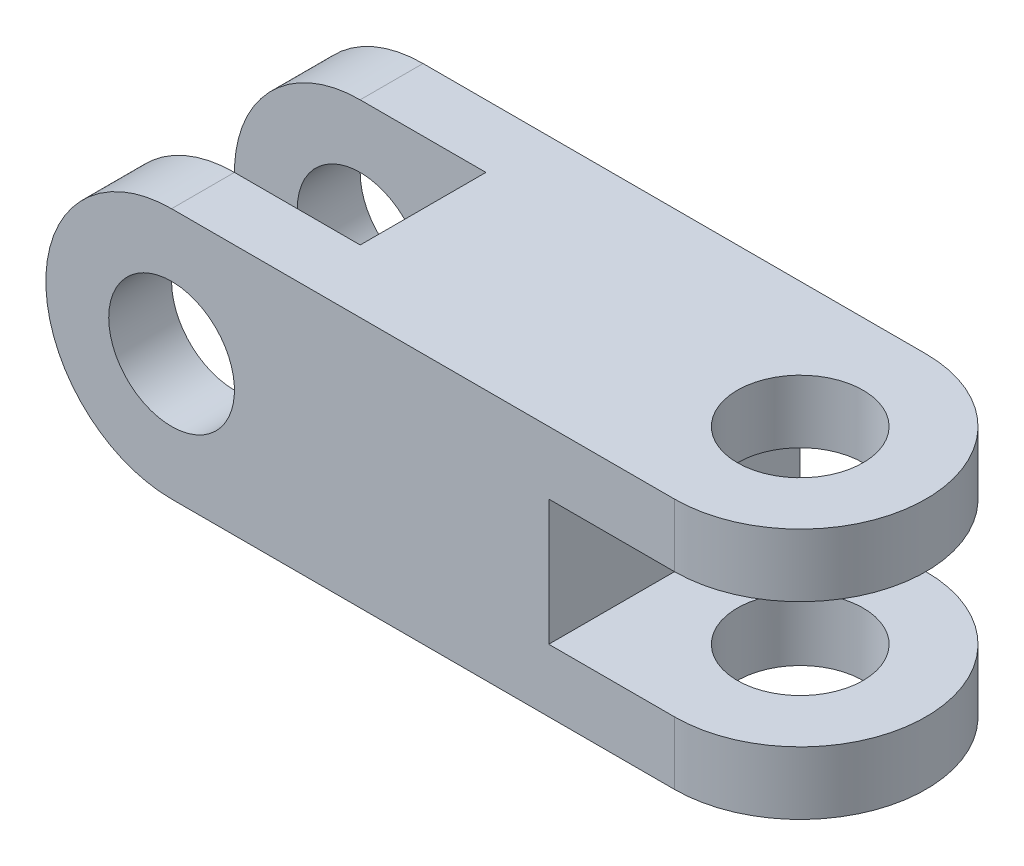
SolidWorks part; units mm, degrees
ref_plane "Plan de face" through (0, 0, 0) normal (0, 0, 1) x (1, 0, 0)
ref_plane "Plan de dessus" through (0, 0, 0) normal (0, 1, 0) x (1, 0, 0)
ref_plane "Plan de droite" through (0, 0, 0) normal (1, 0, 0) x (0, 0, -1)
sketch "Esquisse1" plane through (0, 0, 0) normal (0, 0, 1) x (1, 0, 0)
  line L0 (50, 5) -> (50, 15) construction
  line L1 (0, 0) -> (50, 0)
  line L2 (0, 0) -> (0, 20) construction
  line L3 (0, 20) -> (50, 20)
  line L4 (50, 0) -> (50, 5)
  line L5 (50, 15) -> (30, 15)
  line L6 (50, 15) -> (50, 5) construction
  line L7 (50, 5) -> (30, 5)
  line L8 (30, 15) -> (30, 5)
  line L9 (50, 15) -> (50, 20)
  arc A0 (0, 0) -> (0, 20) centre (0, 10) cw
  circle A1 centre (0, 10) radius 5
  point P11 (50, 10)
  point P12 (50, 10)
  dimension "D2" = 10
  dimension "D1" = 20
  dimension "D3" = 50
  dimension "D4" = 10
  dimension "D5" = 20
extrude "Boss.-Extru.1" add sketch "Esquisse1" along normal blind 20
sketch "Esquisse2" plane through (0, 0, 0) normal (0, 1, 0) x (1, 0, 0)
  line L0 (-10, -5) -> (-10, -15) construction
  line L1 (40, 0) -> (-10, 0)
  line L2 (40, 0) -> (40, -20) construction
  line L3 (40, -20) -> (-10, -20)
  line L4 (-10, 0) -> (-10, -5)
  line L5 (-10, -15) -> (10, -15)
  line L6 (-10, -15) -> (-10, -5) construction
  line L7 (-10, -5) -> (10, -5)
  line L8 (10, -15) -> (10, -5)
  line L9 (-10, -15) -> (-10, -20)
  line L10 (-10, 0) -> (-10, -20) construction
  line L11 (50, -20) -> (0, -20) construction
  line L12 (50, 0) -> (0, 0) construction
  arc A0 (40, 0) -> (40, -20) centre (40, -10) cw
  circle A1 centre (40, -10) radius 5
  point P11 (-10, -10)
  point P12 (-10, -10)
  dimension "D2" = 10
  dimension "D1" = 20
  dimension "D3" = 50
  dimension "D4" = 10
  dimension "D5" = 20
extrude "Boss.-Extru.2" add sketch "Esquisse2" along normal blind 20 separate body
combine bodies "Combiner1" operation type common bodies to combine 102 101
ref_axis "Axe1" through (40, 20, 10) along (0, -1, 0)
ref_axis "Axe2" through (0, 10, 5) along (0, 0, -1)
ref_plane "Plan1" through (0, 0, 10) normal (0, 0, 1) x (1, 0, 0)
ref_plane "Plan2" through (0, 10, 0) normal (0, 1, 0) x (1, 0, 0)
